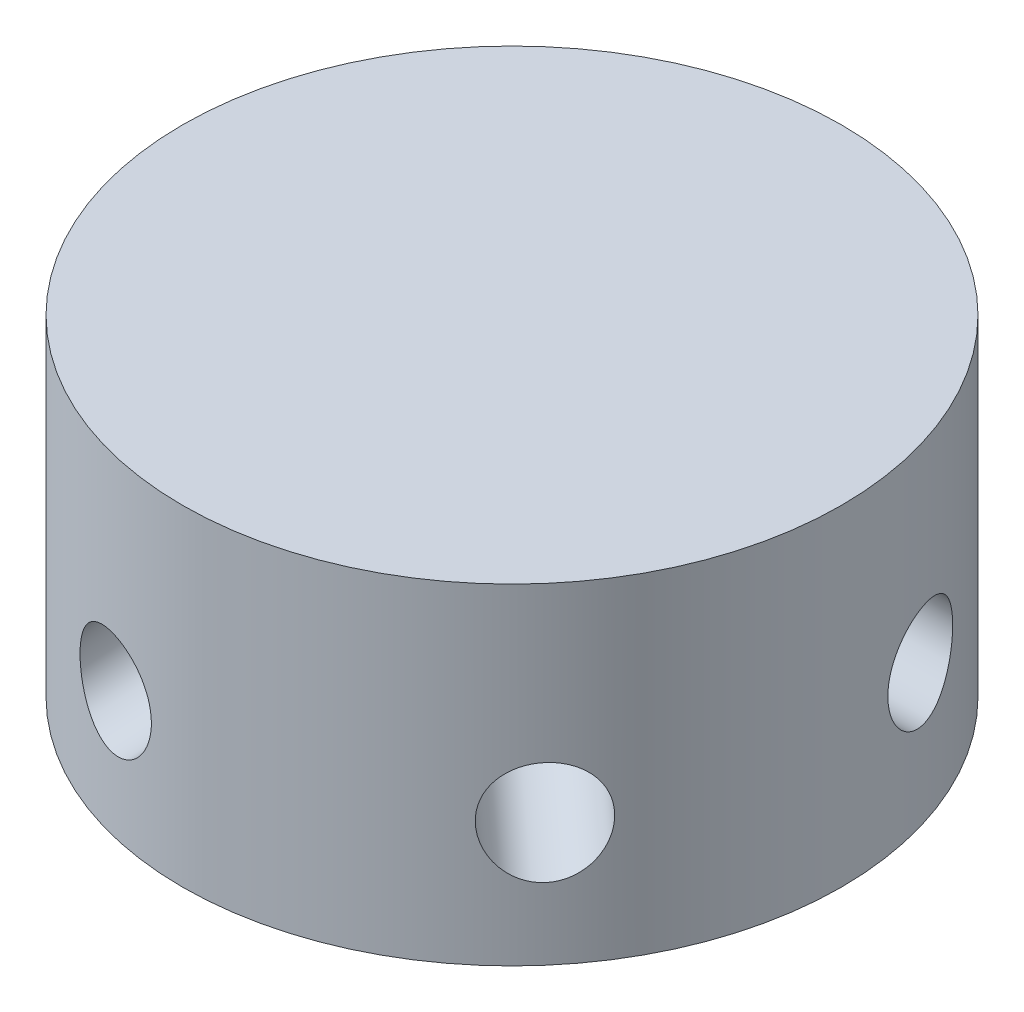
SolidWorks part; units mm, degrees
ref_plane "Front Plane" through (0, 0, 0) normal (0, 0, 1) x (1, 0, 0)
ref_plane "Top Plane" through (0, 0, 0) normal (0, 1, 0) x (1, 0, 0)
ref_plane "Right Plane" through (0, 0, 0) normal (1, 0, 0) x (0, 0, -1)
sketch "Sketch1" plane through (0, 0, 0) normal (0, 1, 0) x (1, 0, 0)
  circle A0 centre (0, 0) radius 10
  dimension "D1" = 20
extrude "base" add sketch "Sketch1" along normal blind 3.0354 and the other way blind 7
ref_axis "6hubaxis" through (0, 5.5, 0) along (0, -1, 0)
ref_plane "Plane1" through (2.6705, -1.0931, 2.7701) normal (-0.6676, 0.2733, -0.6925) x (-0.6559, 0.2243, 0.7208)
sketch "Sketch2" [suppressed] plane through (2.6705, -1.0931, 2.7701) normal (-0.6676, 0.2733, -0.6925) x (-0.6559, 0.2243, 0.7208)
  circle A0 centre (0, 0) radius 1.5 construction
  circle A1 centre (0, 0) radius 1.5
extrude "hole1" [suppressed] cut sketch "Sketch2" against normal through all
pattern_circular "hole1mirror" [suppressed] count 2 over 360 about axis through (0, 5.5, 0) along (0, -1, 0) of bodies 112
ref_plane "Plane2" through (-0.9417, -1.2361, 3.6858) normal (0.2354, 0.309, -0.9215) x (-0.9719, 0.0738, -0.2235)
sketch "Sketch3" plane through (-0.9417, -1.2361, 3.6858) normal (0.2354, 0.309, -0.9215) x (-0.9719, 0.0738, -0.2235)
  circle A0 centre (0, 0) radius 1.5 construction
  circle A1 centre (0, 0) radius 1.5
extrude "hole2" cut sketch "Sketch3" against normal through all
pattern_circular "hole2mirror" count 2 over 360 about axis through (0, 5.5, 0) along (0, -1, 0) of "hole2"
ref_plane "Plane3" through (-3.7178, -1.2361, 0.8061) normal (0.9295, 0.309, -0.2015) x (-0.1912, -0.0636, -0.9795)
sketch "Sketch4" plane through (-3.7178, -1.2361, 0.8061) normal (0.9295, 0.309, -0.2015) x (-0.1912, -0.0636, -0.9795)
  circle A0 centre (0, 0) radius 1.5 construction
  circle A1 centre (0, 0) radius 1.5
extrude "hole3" cut sketch "Sketch4" against normal through all
pattern_circular "hole3mirror" [suppressed] count 2 over 360 about axis through (0, 5.5, 0) along (0, -1, 0) of bodies 117
ref_plane "Plane4" through (3.672, -1.0931, -1.1497) normal (-0.918, 0.2733, 0.2874) x (0.2755, -0.082, 0.9578)
sketch "Sketch5" plane through (3.672, -1.0931, -1.1497) normal (-0.918, 0.2733, 0.2874) x (0.2755, -0.082, 0.9578)
  circle A0 centre (0, 0) radius 1.5 construction
  circle A1 centre (0, 0) radius 1.5
extrude "Cut-Extrude1" cut sketch "Sketch5" against normal through all
ref_plane "Plane5" through (2.8756, -1.2361, 2.4906) normal (-0.7189, 0.309, -0.6227) x (-0.572, 0.2459, 0.7825)
sketch "Sketch6" plane through (2.8756, -1.2361, 2.4906) normal (-0.7189, 0.309, -0.6227) x (-0.572, 0.2459, 0.7825)
  circle A0 centre (0, 0) radius 1.5 construction
  circle A1 centre (0, 0) radius 1.5
extrude "Cut-Extrude2" cut sketch "Sketch6" against normal through all
ref_plane "Plane6" through (-2.6705, -1.0931, -2.7701) normal (0.6676, 0.2733, 0.6925) x (0.7445, -0.2451, -0.621)
sketch "Sketch7" plane through (-2.6705, -1.0931, -2.7701) normal (0.6676, 0.2733, 0.6925) x (0.7445, -0.2451, -0.621)
  circle A0 centre (0, 0) radius 1.5 construction
  circle A1 centre (0, 0) radius 1.5
extrude "Cut-Extrude3" cut sketch "Sketch7" against normal through all
sketch "Sketch9" plane through (0, -7, 0) normal (0, -1, 0) x (1, 0, 0)
  line L0 (-10, 0) -> (10, 0) construction
  circle A0 centre (0, 0) radius 10 construction
  text T0 "6-2"
extrude "Boss-Extrude1" add sketch "Sketch9" along normal blind 1
